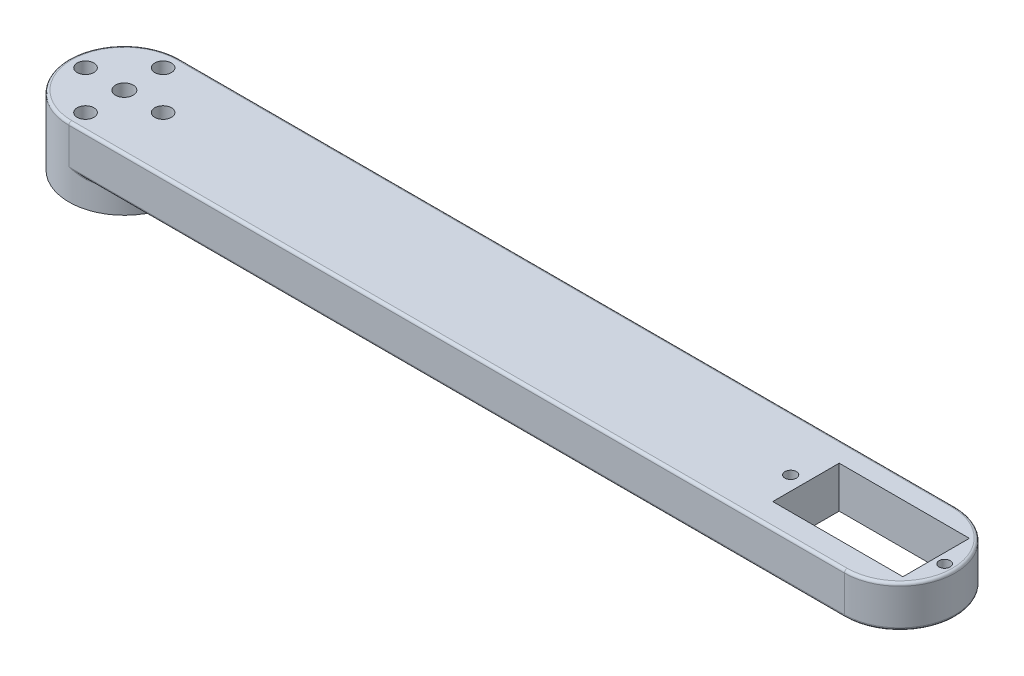
SolidWorks part; units mm, degrees
ref_plane "Front Plane" through (0, 0, 0) normal (0, 0, 1) x (1, 0, 0)
ref_plane "Top Plane" through (0, 0, 0) normal (0, 1, 0) x (1, 0, 0)
ref_plane "Right Plane" through (0, 0, 0) normal (1, 0, 0) x (0, 0, -1)
sketch "Sketch1" plane through (0, 0, 0) normal (0, 1, 0) x (1, 0, 0)
  line L0 (0, 0) -> (140, 0) construction
  line L2 (0, 10) -> (140, 10)
  line L3 (0, -10) -> (140, -10)
  line L4 (146.35, 6.2087) -> (122.85, 6.2087)
  line L5 (146.35, 6.2087) -> (146.35, -5.7913)
  line L6 (146.35, -5.7913) -> (122.85, -5.7913)
  line L7 (122.85, 6.2087) -> (122.85, -5.7913)
  arc A2 (0, 10) -> (0, -10) centre (0, 0) ccw
  arc A3 (140, -10) -> (140, 10) centre (140, 0) ccw
  circle A4 centre (0, 0) radius 1.6
  circle A11 centre (148.101, -0.0081) radius 1.001
  circle A12 centre (120.301, -0.0011) radius 1.0347
  circle A17 centre (7, 0) radius 1.51
  circle A18 centre (0, -7) radius 1.51
  circle A19 centre (-7, 0) radius 1.51
  circle A20 centre (0, 7) radius 1.51
  point P5 (70, 0)
  point P29 (0, 0)
  point P30 (0, 0)
  dimension "D1" = 140
  dimension "D4" = 27.8
  dimension "D5" = 7
  dimension "D2" = 23.5
  dimension "D3" = 12
  dimension "D6" = 4
extrude "Boss-Extrude1" add sketch "Sketch1" along normal blind 7.5
sketch "Sketch6" plane through (0, 0, 0) normal (0, -1, 0) x (1, 0, 0)
  circle A0 centre (0, 0) radius 10
sketch "Sketch7" plane through (0, 0, 0) normal (0, -1, 0) x (1, 0, 0)
  circle A0 centre (0, 0) radius 10
  circle A1 centre (0, 7) radius 1.51
  circle A2 centre (7, 0) radius 1.51
  circle A3 centre (0, -7) radius 1.51
  circle A4 centre (-7, 0) radius 1.51
  circle A5 centre (0, 0) radius 1.6
  point P13 (0, 0)
  dimension "D1" = 4
extrude "Boss-Extrude4" add sketch "Sketch7" along normal blind 5
fillet "Fillet2" radius 0.5 8 edges at (150, 0, 0) (70, 0, -10) (10, 0, 0) (70, 0, 10) (150, 7.5, 0) (70, 7.5, -10) (-10, 7.5, 0) (70, 7.5, 10)
